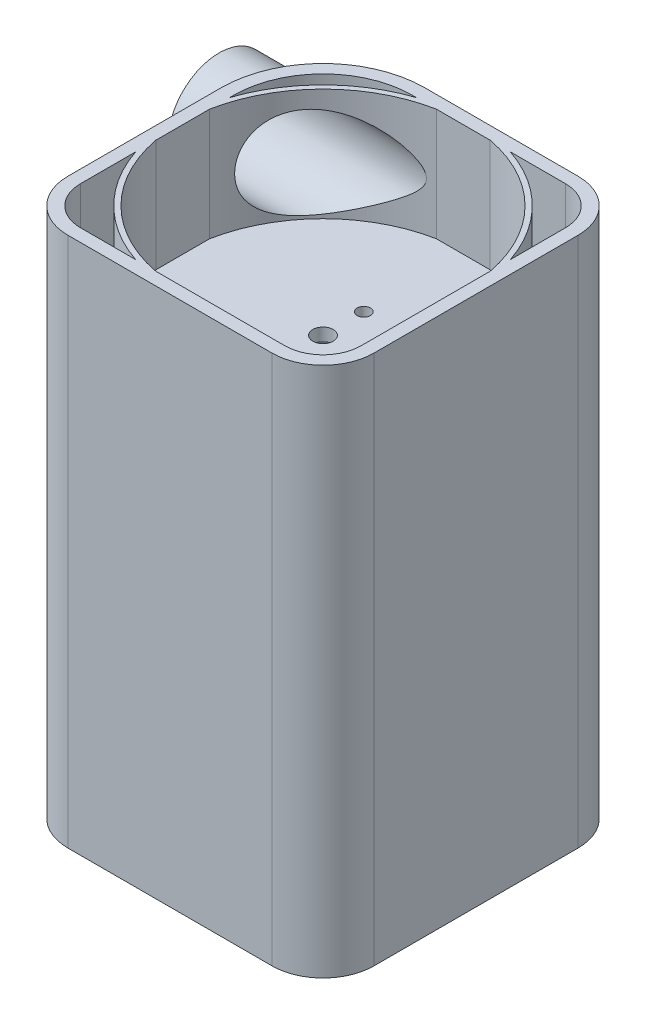
SolidWorks part; units mm, degrees
ref_plane "Front Plane" through (0, 0, 0) normal (0, 0, 1) x (1, 0, 0)
ref_plane "Top Plane" through (0, 0, 0) normal (0, 1, 0) x (1, 0, 0)
ref_plane "Right Plane" through (0, 0, 0) normal (1, 0, 0) x (0, 0, -1)
sketch "Sketch2" plane through (0, 0, 0) normal (0, 1, 0) x (1, 0, 0)
  line L1 (-10, 30) -> (20, 30)
  line L2 (-30, 10) -> (-30, -20)
  line L3 (-20, -30) -> (20, -30)
  line L4 (30, 20) -> (30, -20)
  line L5 (-30, 30) -> (30, -30) construction
  line L6 (-30, -30) -> (30, 30) construction
  arc A0 (-10, 30) -> (-30, 10) centre (-10, 10) ccw
  arc A1 (-30, -20) -> (-20, -30) centre (-20, -20) ccw
  arc A2 (20, -30) -> (30, -20) centre (20, -20) ccw
  arc A3 (20, 30) -> (30, 20) centre (20, 20) cw
  point P0 (0, 0)
  dimension "D3" = 20
  dimension "D4" = 10
  dimension "D1" = 60
  dimension "D2" = 60
extrude "Boss-Extrude1" add sketch "Sketch2" along normal blind 82
shell "Shell1" thickness 2.5 removed face at (0.9911, 0, 0.9911)
sketch "Sketch5" plane through (0, 82, 0) normal (0, 1, 0) x (1, 0, 0)
  line L4 (-30, 10) -> (-30, -20)
  line L5 (-20, -30) -> (20, -30)
  line L6 (30, -20) -> (30, 20)
  line L7 (20, 30) -> (-10, 30)
  line L8 (-30, 10) -> (-30, -20)
  line L9 (-20, -30) -> (20, -30)
  line L10 (30, -20) -> (30, 20)
  line L11 (20, 30) -> (-10, 30)
  arc A4 (-10, 30) -> (-30, 10) centre (-10, 10) ccw
  arc A5 (-30, -20) -> (-20, -30) centre (-20, -20) ccw
  arc A6 (20, -30) -> (30, -20) centre (20, -20) ccw
  arc A7 (30, 20) -> (20, 30) centre (20, 20) ccw
  arc A8 (-10, 30) -> (-30, 10) centre (-10, 10) ccw
  arc A9 (-30, -20) -> (-20, -30) centre (-20, -20) ccw
  arc A10 (20, -30) -> (30, -20) centre (20, -20) ccw
  arc A11 (30, 20) -> (20, 30) centre (20, 20) ccw
  dimension "D1" = 0
extrude "Boss-Extrude2" add sketch "Sketch5" along normal blind 22
shell "Shell2" thickness 2.5 removed face at (0.9911, 104, 0.9911)
ref_plane "Plane1" through (0, 114, 0) normal (0, 1, 0) x (1, 0, 0)
sketch "Sketch6" plane through (0, 82, 0) normal (0, 1, 0) x (1, 0, 0)
  line L0 (0, 0) -> (-0.7232, -28.991) construction
  line L1 (0, 0) -> (29, 0) construction
  line L2 (-0.7232, -28.991) -> (-0.6983, -27.9913)
  line L3 (28, 0) -> (29, 0)
  arc A0 (29, 0) -> (-0.7232, -28.991) centre (0, 0) ccw
  arc A1 (28, 0) -> (-0.6983, -27.9913) centre (0, 0) ccw
  dimension "D1" = 58
  dimension "D2" = 1
extrude "Boss-Extrude7" add sketch "Sketch6" along normal up to surface (22 mm away) up to face at (0.9911, 104, 0.9911)
sketch "Sketch7" plane through (0, 82, 0) normal (0, 1, 0) x (1, 0, 0)
  circle A0 centre (0, 0) radius 2
  circle A1 centre (0, 8) radius 1.3
  circle A2 centre (0, -8) radius 1.3
  dimension "D1" = 4
  dimension "D2" = 2.6
  dimension "D3" = 16
  dimension "D4" = 8
extrude "Cut-Extrude1" cut sketch "Sketch7" against normal blind 10
sketch "Sketch8" plane through (0, 79.5, 0) normal (0, -1, 0) x (1, 0, 0)
  circle A0 centre (0, 0) radius 15.2
  circle A1 centre (0, 0) radius 16
  dimension "D1" = 0.8
  dimension "D2" = 32
extrude "Boss-Extrude8" add sketch "Sketch8" along normal blind 6
ref_plane "Plane2" through (-38.5, 0, 0) normal (-1, 0, 0) x (0, 0, 1)
sketch "Sketch10" plane through (-38.5, 0, 0) normal (-1, 0, 0) x (0, 0, 1)
  circle A0 centre (-18.1447, 91.6227) radius 10
  circle A1 centre (-18.1447, 91.6227) radius 9
  dimension "D1" = 20
  dimension "D2" = 1
extrude "Boss-Extrude9" add sketch "Sketch10" against normal blind 30
sketch "Sketch13" plane through (-38.5, 0, 0) normal (-1, 0, 0) x (0, 0, 1)
  circle A0 centre (-18.1447, 91.6227) radius 9 construction
  circle A1 centre (-18.1447, 91.6227) radius 9
extrude "Cut-Extrude2" cut sketch "Sketch13" against normal blind 40
sketch "Sketch14" plane through (0, 104, 0) normal (0, 1, 0) x (1, 0, 0)
  line L0 (-27.5, 5.2678) -> (-27.5, -5.2678) construction
  line L1 (-5.2678, -27.5) -> (20, -27.5) construction
  line L2 (27.5, -20) -> (27.5, 5.2678) construction
  line L3 (5.2678, 27.5) -> (-5.2678, 27.5) construction
  line L4 (-27.5, 5.2678) -> (-27.5, -5.2678)
  line L5 (-5.2678, -27.5) -> (20, -27.5)
  line L6 (27.5, -20) -> (27.5, 5.2678)
  line L7 (5.2678, 27.5) -> (-5.2678, 27.5)
  arc A0 (-27.5, -5.2678) -> (-5.2678, -27.5) centre (0, 0) ccw construction
  arc A1 (20, -27.5) -> (27.5, -20) centre (20, -20) ccw construction
  arc A2 (27.5, 5.2678) -> (5.2678, 27.5) centre (0, 0) ccw construction
  arc A3 (-5.2678, 27.5) -> (-27.5, 5.2678) centre (0, 0) ccw construction
  arc A4 (-27.5, -5.2678) -> (-5.2678, -27.5) centre (0, 0) ccw
  arc A5 (20, -27.5) -> (27.5, -20) centre (20, -20) ccw
  arc A6 (27.5, 5.2678) -> (5.2678, 27.5) centre (0, 0) ccw
  arc A7 (-5.2678, 27.5) -> (-27.5, 5.2678) centre (0, 0) ccw
extrude "Cut-Extrude3" cut sketch "Sketch14" against normal up to surface (22 mm away) up to face at (-3.6423, 82, -4.7841)
sketch "Sketch15" plane through (0, 79.5, 0) normal (0, -1, 0) x (1, 0, 0)
  arc A0 (3.7036, -21.3934) -> (-2.0086, -21.3934) centre (0.8475, -22.3113) ccw
  arc A1 (-2.0086, -23.2292) -> (3.7036, -23.2292) centre (0.8475, -22.3113) ccw
  ellipse E0 centre (0.8475, -22.3113) end of major axis (-6.1525, -22.3113) minor radius 1.0054 (3.7036, -23.2292) -> (3.7036, -21.3934) ccw
  ellipse E1 centre (0.8475, -22.3113) end of major axis (-6.1525, -22.3113) minor radius 1.0054 (-2.0086, -21.3934) -> (-2.0086, -23.2292) ccw
  dimension "D2" = 14
extrude "Boss-Extrude10" add sketch "Sketch15" along normal blind 40
